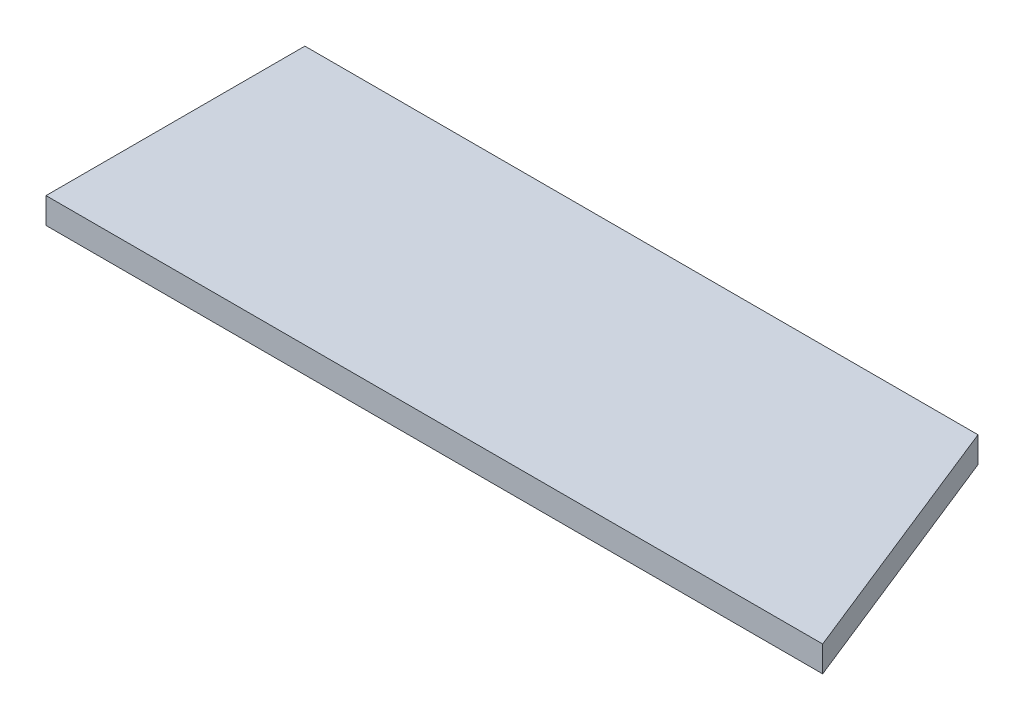
SolidWorks part; units mm, degrees
ref_plane "Спереди" through (0, 0, 0) normal (0, 0, 1) x (1, 0, 0)
ref_plane "Сверху" through (0, 0, 0) normal (0, 1, 0) x (1, 0, 0)
ref_plane "Справа" through (0, 0, 0) normal (1, 0, 0) x (0, 0, -1)
sketch "Эскиз1" plane through (0, 0, 0) normal (0, 1, 0) x (1, 0, 0)
  line L0 (0, 0) -> (150, 0)
  line L1 (150, 0) -> (130, 50)
  line L2 (130, 50) -> (0, 50)
  line L3 (0, 50) -> (0, 0)
extrude "Бобышка-Вытянуть1" add sketch "Эскиз1" along normal blind 5
